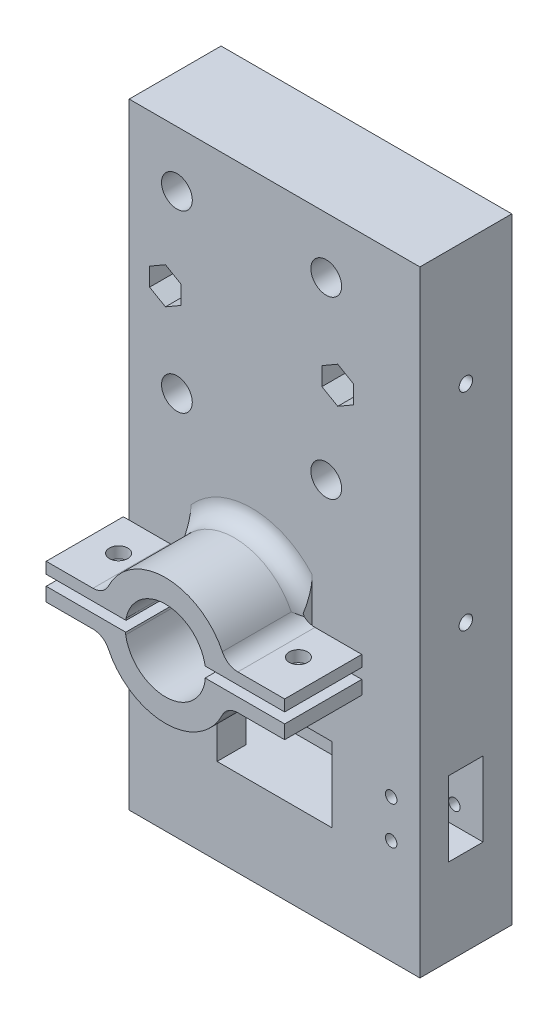
SolidWorks part; units mm, degrees
other "Markup1"
sketch "Sketch8" plane through (21.3115, 25, 0) normal (0.306, 0.1864, -0.9336) x (-0.9512, 0.0181, -0.3081)
ref_plane "Front Plane" through (0, 0, 0) normal (0, 0, 1) x (1, 0, 0)
ref_plane "Top Plane" through (0, 0, 0) normal (0, 1, 0) x (1, 0, 0)
ref_plane "Right Plane" through (0, 0, 0) normal (1, 0, 0) x (0, 0, -1)
sketch "Sketch1" plane through (0, 0, 0) normal (0, 0, 1) x (1, 0, 0)
  line L0 (0, 25) -> (0, -25) construction
  line L1 (21.3115, 25) -> (-21.3115, 25)
  line L2 (21.3115, 25) -> (21.3115, -25)
  line L3 (21.3115, -25) -> (-21.3115, -25)
  line L4 (-21.3115, 25) -> (-21.3115, -25)
  line L5 (21.3115, 25) -> (-21.3115, -25) construction
  line L6 (21.3115, -25) -> (-21.3115, 25) construction
  line L7 (-21.3115, 0) -> (21.3115, 0) construction
  circle A0 centre (-13, -15.25) radius 2.677
  circle A1 centre (13, -15.25) radius 2.677
  circle A2 centre (13, 15.25) radius 2.677
  circle A3 centre (-13, 15.25) radius 2.677
  point P0 (0, 0)
  dimension "D1" = 30.5
  dimension "D2" = 26
  dimension "D3" = 50
extrude "Boss-Extrude1" add sketch "Sketch1" along normal blind 16
sketch "Sketch2" plane through (0, 0, 0) normal (0, 0, 1) x (1, 0, 0)
  circle A0 centre (0, 0) radius 11.04
  dimension "D1" = 22.08
extrude "Cut-Extrude2" cut sketch "Sketch2" along normal blind 11
sketch "Sketch3" plane through (0, 0, 0) normal (0, 0, -1) x (-1, 0, 0)
  line L0 (0, 0) -> (-18.0234, 0) construction
  line L1 (0, 0) -> (0, 5.0894) construction
  circle A0 centre (-15, 0) radius 1.75
  circle A1 centre (15, 0) radius 1.75
  dimension "D1" = 15
  dimension "D2" = 3.5
extrude "Cut-Extrude3" cut sketch "Sketch3" against normal blind 10
sketch "Sketch9" plane through (0, 0, 0) normal (0, 0, -1) x (-1, 0, 0)
  line L0 (0, -11.04) -> (0, 11.04) construction
  line L1 (-15, 3.1754) -> (-17.75, 1.5877)
  line L2 (-17.75, 1.5877) -> (-17.75, -1.5877)
  line L3 (-17.75, -1.5877) -> (-15, -3.1754)
  line L4 (-15, -3.1754) -> (-12.25, -1.5877)
  line L5 (-12.25, -1.5877) -> (-12.25, 1.5877)
  line L6 (-12.25, 1.5877) -> (-15, 3.1754)
  line L7 (12.25, 1.5877) -> (15, 3.1754)
  line L8 (12.25, -1.5877) -> (12.25, 1.5877)
  line L9 (15, -3.1754) -> (12.25, -1.5877)
  line L10 (17.75, -1.5877) -> (15, -3.1754)
  line L11 (17.75, 1.5877) -> (17.75, -1.5877)
  line L12 (15, 3.1754) -> (17.75, 1.5877)
  circle A0 centre (-15, 0) radius 2.75 construction
  circle A1 centre (0, 0) radius 11.04 construction
  point P1 (-17.75, 0)
  dimension "D1" = 5.5
extrude "Cut-Extrude6" cut sketch "Sketch9" against normal through all from offset 5 offset against normal yes
sketch "Sketch30" plane through (0, -25, 0) normal (0, -1, 0) x (1, 0, 0)
  line L1 (-21.3115, 16) -> (21.3115, 16)
  line L2 (-21.3115, 16) -> (-21.3115, 0)
  line L3 (-21.3115, 0) -> (21.3115, 0)
  line L4 (21.3115, 16) -> (21.3115, 0)
extrude "Boss-Extrude8" add sketch "Sketch30" along normal blind 20.23
sketch "Sketch10" plane through (0, 0, 0) normal (0, 0, 1) x (1, 0, 0)
  line L0 (21.3115, -45.23) -> (-21.3115, -45.23)
  line L2 (-21.3115, -45.23) -> (-21.3115, -67.23)
  line L3 (-21.3115, -67.23) -> (21.3115, -67.23)
  line L4 (21.3115, -67.23) -> (21.3115, -45.23)
  dimension "D1" = 22
extrude "Boss-Extrude2" add sketch "Sketch10" along normal up to surface (16 mm away) up to face at (15, 0, 16)
sketch "Sketch14" plane through (-21.3115, 0, 0) normal (-1, 0, 0) x (0, 0, 1)
  line L0 (16, -67.23) -> (0, -67.23) construction
  line L1 (5, -67.23) -> (11, -67.23)
  line L2 (5, -67.23) -> (5, -54.23)
  line L3 (5, -54.23) -> (11, -54.23)
  line L4 (11, -67.23) -> (11, -54.23)
  line L7 (0, -67.23) -> (16, -67.23) construction
  point P6 (8, -67.23)
  point P7 (8, -67.23)
  dimension "D1" = 13
  dimension "D2" = 6
extrude "Cut-Extrude7" cut sketch "Sketch14" against normal through all
sketch "Sketch16" plane through (21.3115, 0, 0) normal (1, 0, 0) x (0, 0, -1)
  line L0 (-8, -54.23) -> (-8, 25)
  line L1 (-11, -54.23) -> (-5, -54.23) construction
  line L2 (-16, 25) -> (0, 25) construction
  line L4 (-16, 25) -> (0, 25)
  line L5 (-16, 25) -> (-16, -54.23)
  line L6 (-16, -54.23) -> (0, -54.23)
  line L7 (0, 25) -> (0, -54.23)
  line M6 (-11, -54.23) -> (-5, -54.23)
  line M9 (0, -67.23) -> (0, 25)
  line M10 (0, 25) -> (-16, 25)
  line M11 (-16, 25) -> (-16, -67.23)
extrude "Boss-Extrude3" add sketch "Sketch16" along normal blind 8 contours L6 L0 M11 M6 M10 | L6 L0 M6 M9 M10
sketch "Sketch17" plane through (29.3115, 0, 0) normal (1, 0, 0) x (0, 0, -1)
  line L0 (-8, -54.23) -> (-8, 25)
  line L1 (-16, -54.23) -> (0, -54.23) construction
  line L2 (0, 25) -> (-16, 25) construction
  line L3 (-8, -14.615) -> (0, -14.615)
  line L4 (0, -54.23) -> (0, 25) construction
  circle A0 centre (-8, 3.385) radius 1.175
  circle A1 centre (-8, -32.615) radius 1.175
  point P8 (-8, -14.615)
  dimension "D2" = 2.35
  dimension "D1" = 18
extrude "Cut-Extrude9" cut sketch "Sketch17" against normal blind 8 contours L0 A0 | L0 A0 | A1 L0 | A1 L0
sketch "Sketch18" plane through (0, 0, 0) normal (0, 0, -1) x (-1, 0, 0)
  line L0 (-25.3115, -54.23) -> (-25.3115, 25)
  line L1 (-29.3115, -54.23) -> (-21.3115, -54.23) construction
  line L2 (-29.3115, 25) -> (21.3115, 25) construction
  line L3 (-25.3115, -14.615) -> (-29.3115, -14.615)
  line L4 (-26.2115, 5.385) -> (-24.4115, 5.385)
  line L5 (-26.2115, 5.385) -> (-26.2115, 1.385)
  line L6 (-26.2115, 1.385) -> (-24.4115, 1.385)
  line L7 (-24.4115, 5.385) -> (-24.4115, 1.385)
  line L8 (-26.2115, 5.385) -> (-24.4115, 1.385) construction
  line L9 (-26.2115, 1.385) -> (-24.4115, 5.385) construction
  line L10 (-29.3115, -54.23) -> (-29.3115, 25) construction
  line L11 (-26.2115, -30.615) -> (-24.4115, -30.615)
  line L12 (-24.4115, -34.615) -> (-24.4115, -30.615)
  line L13 (-26.2115, -34.615) -> (-24.4115, -34.615)
  line L14 (-26.2115, -34.615) -> (-26.2115, -30.615)
  point P6 (-25.3115, 3.385)
  point P11 (-25.3115, -14.615)
  dimension "D1" = 18
  dimension "D2" = 4
  dimension "D3" = 1.8
extrude "Cut-Extrude10" cut sketch "Sketch18" against normal blind 10.2 contours L7 L4 L0 L6 | L5 L6 L0 L4 | L14 L11 L12 L13
sketch "Sketch15" plane through (0, 0, 0) normal (0, 0, -1) x (-1, 0, 0)
  line L0 (21.3115, -67.23) -> (-21.3115, -67.23) construction
  line L1 (-29.3115, -23.2996) -> (21.3115, -23.2996)
  line L2 (-21.3115, -67.23) -> (-21.3115, -54.23)
  line L3 (-29.3115, -54.23) -> (-29.3115, 25) construction
  line L4 (-4, -23.2996) -> (-4, -67.23)
  line L7 (-21.3115, -67.23) -> (-21.3115, -54.23) construction
  line L8 (-21.3115, -54.23) -> (-21.3115, -67.23) construction
  line L9 (-21.3115, -60.73) -> (21.3115, -60.73)
  line L10 (21.3115, 25) -> (21.3115, -67.23) construction
  line L11 (21.3115, -60.73) -> (21.3115, -28)
  line L12 (21.3115, -28) -> (0, -28)
  line L13 (0, -28) -> (0, -67.23)
  circle A2 centre (16.3115, -64.03) radius 1
  circle A4 centre (16.3115, -57.43) radius 1
  point P11 (-21.3115, -67.23)
  dimension "D1" = 5
  dimension "D2" = 3.2
extrude "Cut-Extrude8" cut sketch "Sketch15" against normal through all and the other way through all
sketch "Sketch6" plane through (0, -54.23, 0) normal (0, -1, 0) x (1, 0, 0)
  line L0 (21.3115, 11) -> (-21.3115, 11) construction
  line L1 (4.517, 11) -> (-4.517, 11)
  line L2 (4.517, 11) -> (4.517, 14.85)
  line L3 (4.517, 14.85) -> (-4.517, 14.85)
  line L4 (-4.517, 11) -> (-4.517, 14.85)
  line L5 (4.517, 11) -> (-4.517, 14.85) construction
  line L6 (4.517, 14.85) -> (-4.517, 11) construction
  point P0 (0, 12.925)
  dimension "D1" = 3.85
extrude "Cut-Extrude5" cut sketch "Sketch6" against normal blind 50 and the other way through all
sketch "Sketch20" plane through (0, -54.23, 0) normal (0, -1, 0) x (-1, 0, 0)
  line L1 (-21.3115, -16) -> (-29.3115, -16)
  line L2 (-21.3115, -16) -> (-21.3115, 0)
  line L3 (-21.3115, 0) -> (-29.3115, 0)
  line L4 (-29.3115, -16) -> (-29.3115, 0)
extrude "Boss-Extrude5" add sketch "Sketch20" along normal up to surface (13 mm away) up to face at (0, -67.23, 13.2125)
sketch "Sketch21" plane through (0, -67.23, 0) normal (0, -1, 0) x (-1, 0, 0)
  line L0 (-29.3115, -16) -> (-29.3115, 0) construction
  line L1 (-21.3115, -11) -> (-29.3115, -11)
  line L2 (-21.3115, -11) -> (-21.3115, -5)
  line L3 (-21.3115, -5) -> (-29.3115, -5)
  line L4 (-29.3115, -11) -> (-29.3115, -5)
extrude "Cut-Extrude11" cut sketch "Sketch21" against normal up to surface (13 mm away) up to face at (0, -54.23, 9)
sketch "Sketch22" plane through (0, 0, 0) normal (0, 0, -1) x (-1, 0, 0)
  line L0 (21.3115, -67.23) -> (-29.3115, -67.23) construction
  line L1 (-29.3115, -67.23) -> (-29.3115, 25) construction
  circle A0 centre (-24.3115, -64.03) radius 1
  circle A3 centre (-24.3115, -57.43) radius 1
  dimension "D1" = 2
  dimension "D2" = 3.2
  dimension "D3" = 5
  dimension "D4" = 6.6
  dimension "D5" = 2
  dimension "D6" = 5
extrude "Cut-Extrude12" cut sketch "Sketch22" against normal through all
sketch "Sketch24" plane through (0, -67.23, 0) normal (0, -1, 0) x (1, 0, 0)
  line L1 (-21.3115, 5) -> (29.3115, 5)
  line L2 (-21.3115, 5) -> (-21.3115, 0)
  line L3 (-21.3115, 0) -> (29.3115, 0)
  line L4 (29.3115, 5) -> (29.3115, 0)
extrude "Boss-Extrude6" add sketch "Sketch24" along normal blind 15
sketch "Sketch25" plane through (0, 0, 5) normal (0, 0, 1) x (1, 0, 0)
  line L0 (29.3115, -82.23) -> (-21.3115, -82.23) construction
  line L1 (-21.3115, -82.23) -> (29.3115, -82.23)
  line L2 (-21.3115, -82.23) -> (-21.3115, -67.23)
  line L3 (-21.3115, -67.23) -> (29.3115, -67.23)
  line L4 (29.3115, -82.23) -> (29.3115, -67.23)
extrude "Boss-Extrude7" add sketch "Sketch25" along normal up to surface (11 mm away) up to face at (23.3115, -64.03, 16)
sketch "Sketch26" plane through (0, -82.23, 0) normal (0, -1, 0) x (1, 0, 0)
  line L0 (4, 16) -> (4, 0)
  line L1 (29.3115, 16) -> (-21.3115, 16) construction
  line L2 (-21.3115, 0) -> (29.3115, 0) construction
  line L3 (4, 8) -> (-21.3115, 8)
  line L4 (-21.3115, 16) -> (-21.3115, 0) construction
  circle A0 centre (-14, 8) radius 1
  circle A1 centre (22, 8) radius 1
  dimension "D1" = 2
  dimension "D2" = 18
extrude "Cut-Extrude13" cut sketch "Sketch26" against normal blind 10 contours L3 A0 | L3 A0 | A1
sketch "Sketch27" plane through (0, 0, 0) normal (0, 0, -1) x (-1, 0, 0)
  line L0 (-24.4115, -34.615) -> (-24.4115, -30.615) construction
  line L1 (-24.0015, -77.33) -> (-20.0015, -77.33)
  line L2 (-24.0015, -77.33) -> (-24.0015, -79.13)
  line L3 (-24.0015, -79.13) -> (-20.0015, -79.13)
  line L4 (-20.0015, -77.33) -> (-20.0015, -79.13)
  line L5 (-24.0015, -77.33) -> (-20.0015, -79.13) construction
  line L6 (-24.0015, -79.13) -> (-20.0015, -77.33) construction
  line L8 (-26.2115, -34.615) -> (-24.4115, -34.615) construction
  line L12 (-29.3115, -82.23) -> (-29.3115, 25) construction
  line L13 (21.3115, -82.23) -> (-29.3115, -82.23) construction
  line L14 (-29.3115, -49.5626) -> (21.3115, -49.5626)
  line L15 (21.3115, 25) -> (21.3115, -82.23) construction
  line L16 (-4, -49.5626) -> (-4, -82.23)
  line L17 (16.0015, -79.13) -> (12.0015, -79.13)
  line L18 (12.0015, -77.33) -> (12.0015, -79.13)
  line L19 (16.0015, -77.33) -> (12.0015, -77.33)
  line L20 (16.0015, -77.33) -> (16.0015, -79.13)
  point P0 (-22.0015, -78.23)
  dimension "D1" = 7.31
  dimension "D2" = 3.1
extrude "Cut-Extrude14" cut sketch "Sketch27" against normal blind 10.2 contours L4 L1 L2 L3 | L20 L19 L18 L17
sketch "Sketch29" plane through (0, 0, 16) normal (0, 0, 1) x (1, 0, 0)
  line L0 (-16.3115, -57.43) -> (24.3115, -64.03)
  line L1 (24.3115, -57.43) -> (-16.3115, -64.03)
  line L2 (-16.3115, -57.43) -> (24.3115, -57.43)
  line L3 (-16.3115, -57.43) -> (-16.3115, -64.03)
  line L4 (-16.3115, -64.03) -> (24.3115, -64.03)
  line L5 (24.3115, -57.43) -> (24.3115, -64.03)
  line L7 (-6, -54.23) -> (14, -54.23)
  line L8 (-6, -54.23) -> (-6, -67.23)
  line L9 (-6, -67.23) -> (14, -67.23)
  line L10 (14, -54.23) -> (14, -67.23)
  line L11 (-6, -54.23) -> (14, -67.23) construction
  line L12 (-6, -67.23) -> (14, -54.23) construction
  circle A0 centre (-16.3115, -57.43) radius 1 construction
  point P4 (4, -60.73)
  dimension "D1" = 13
  dimension "D2" = 20
extrude "Cut-Extrude15" cut sketch "Sketch29" against normal up to surface (5 mm away) contours L10 L7 L8 L2 | L10 L2 L8 L0 L1 | L0 L8 L1 | L10 L4 L8 L9 | L10 L0 L1 L8 L4 | L10 L1 L0 up to face at (-16.3115, -65.03, 11)
sketch "Sketch31" plane through (0, 0, 0) normal (0, 0, -1) x (-1, 0, 0)
  line L5 (-4.5, 14.04) -> (4.5, 14.04)
  line L6 (-4.5, 14.04) -> (-4.5, 8.04)
  line L7 (-4.5, -8.04) -> (4.5, -8.04)
  line L8 (-4.5, -8.04) -> (-4.5, -14.04)
  line L9 (-4.5, -14.04) -> (4.5, -14.04)
  line L10 (4.5, -8.04) -> (4.5, -14.04)
  line L11 (-4.5, -8.04) -> (4.5, -14.04) construction
  line L12 (-4.5, -14.04) -> (4.5, -8.04) construction
  line L13 (-4.5, 8.04) -> (4.5, 8.04)
  line L14 (4.5, 14.04) -> (4.5, 8.04)
  line L15 (-4.5, 14.04) -> (4.5, 8.04) construction
  line L16 (-4.5, 8.04) -> (4.5, 14.04) construction
  circle A1 centre (0, 0) radius 11.04 construction
  point P0 (-11.04, 0)
  point P1 (0, 11.04)
  point P8 (0, -11.04)
  dimension "D1" = 6
  dimension "D2" = 9
  dimension "D3" = 9
  dimension "D4" = 6
extrude "Cut-Extrude16" cut sketch "Sketch31" against normal up to surface (11 mm away) up to face at (0, -1.8734, 11)
sketch "Sketch32" plane through (0, 0, 16) normal (0, 0, 1) x (1, 0, 0)
  line L24 (10.5609, -36.9231) -> (20.76, -36.9231)
  line L25 (-18.3513, -38.8888) -> (-6.8513, -38.8888)
  line L27 (-18.3513, -40.6918) -> (-6.9132, -40.6918)
  line L29 (-6.8513, -38.5648) -> (-6.8513, -38.8888)
  line L30 (-6.9132, -41.0991) -> (-6.9132, -40.6918)
  line L31 (6.9132, -41.0991) -> (6.9132, -40.6918)
  line L32 (6.8607, -38.8888) -> (6.8513, -38.5648)
  line L33 (6.8607, -38.8888) -> (18.3513, -38.8888)
  line L34 (6.9132, -40.6918) -> (18.3513, -40.6918)
  line L35 (-20.76, -36.9231) -> (-10.5609, -36.9231)
  line L36 (-20.76, -36.9231) -> (-20.76, -38.8888)
  line L37 (-20.76, -43.0769) -> (-10.5609, -43.0769)
  line L38 (20.76, -36.9231) -> (20.76, -38.8888)
  line L39 (10.5609, -43.0769) -> (20.76, -43.0769)
  line L40 (-18.3513, -38.8888) -> (-20.76, -38.8888)
  line L41 (-18.3513, -40.6918) -> (-20.76, -40.6918)
  line L42 (18.3513, -38.8888) -> (20.76, -38.8888)
  line L43 (18.3513, -40.6918) -> (20.76, -40.6918)
  line L44 (-20.76, -40.6918) -> (-20.76, -43.0769)
  line L45 (20.76, -40.6918) -> (20.76, -43.0769)
  line L46 (0, 0) -> (0, -82.23) construction
  line L47 (29.3115, -82.23) -> (-21.3115, -82.23) construction
  arc A0 (-6.9132, -41.0991) -> (6.9132, -41.0991) centre (0, -40) ccw
  arc A1 (-10.5609, -43.0769) -> (10.5609, -43.0769) centre (0, -40) ccw
  arc A2 (10.5609, -36.9231) -> (-10.5609, -36.9231) centre (0, -40) ccw
  arc A3 (6.8513, -38.5648) -> (-6.8513, -38.5648) centre (0, -40) ccw
  point P15 (0, 0)
  dimension "D1" = 40
extrude "Boss-Extrude9" add sketch "Sketch32" along normal blind 15
sketch "Sketch35" plane through (0, 0, 16) normal (0, 0, 1) x (1, 0, 0)
  line L0 (0, 0) -> (0, -82.23) construction
  line L1 (29.3115, -82.23) -> (-21.3115, -82.23) construction
  circle A0 centre (0, -40) radius 7.01
  point P8 (0, 0)
  point P9 (0, 0)
  point P10 (0, 0)
  dimension "D1" = 14.02
  dimension "D2" = 40
extrude "Cut-Extrude17" cut sketch "Sketch35" against normal through all
sketch "Sketch46" plane through (0, -82.23, 0) normal (0, -1, 0) x (1, 0, 0)
  line L0 (29.3115, 16) -> (-21.3115, 16) construction
  line L2 (-20.76, 31) -> (-20.76, 16) construction
  line L3 (20.76, 31) -> (20.76, 16) construction
  circle A0 centre (-15.66, 23.5) radius 1.6
  circle A1 centre (15.66, 23.5) radius 1.6
  dimension "D1" = 7.5
  dimension "D3" = 5.1
  dimension "D2" = 5.1
extrude "Cut-Extrude29" cut sketch "Sketch46" against normal through all
sketch "Sketch47" plane through (0, 0, 0) normal (0, 1, 0) x (1, 0, 0)
  line L0 (-10.5609, -31) -> (-10.5609, -16) construction
  line L1 (-20.76, -16) -> (-10.5609, -16)
  line L2 (-20.76, -16) -> (-20.76, -17.5701)
  line L3 (-20.76, -17.5701) -> (-10.5609, -17.5701)
  line L4 (-10.5609, -16) -> (-10.5609, -17.5701)
  line L5 (0, 0) -> (0, -33.2951) construction
  line L6 (20.76, -17.5701) -> (10.5609, -17.5701)
  line L7 (10.5609, -16) -> (10.5609, -17.5701)
  line L8 (20.76, -16) -> (10.5609, -16)
  line L9 (20.76, -16) -> (20.76, -17.5701)
extrude "Cut-Extrude30" cut sketch "Sketch47" against normal through all
fillet "Fillet1" radius 3 2 edges at (0, -29, 16) (0, -51, 16)
fillet "Fillet2" radius 3 4 edges at (-10.5609, -43.0769, 25) (-10.5609, -36.9231, 25) (10.5609, -36.9231, 25) (10.5609, -43.0769, 25)
